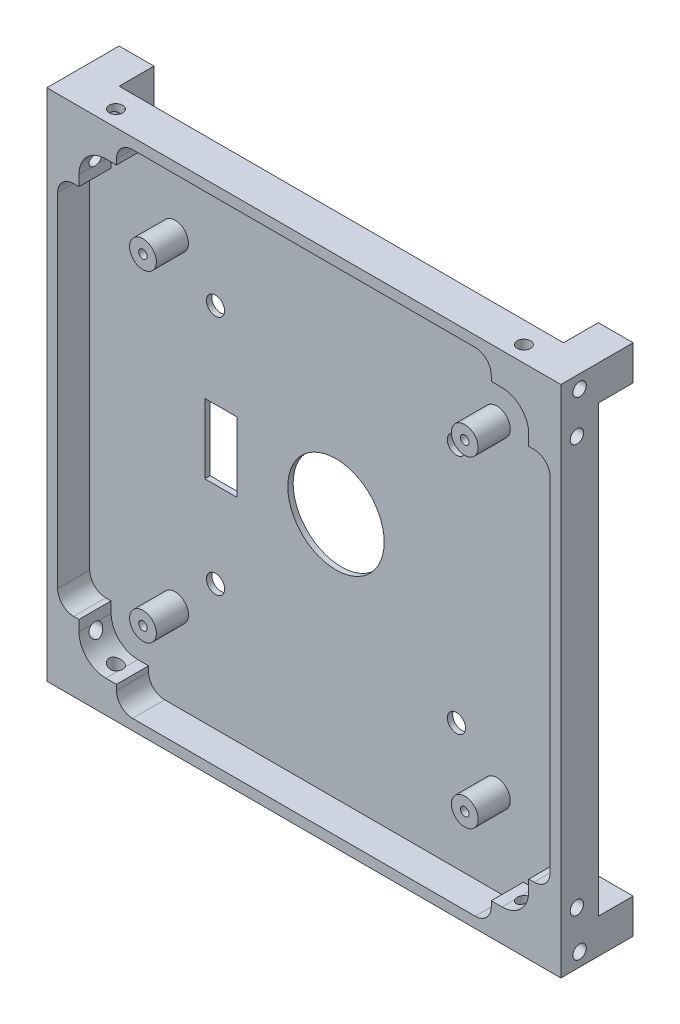
SolidWorks part; units mm, degrees
material "7075-T6 (SN)"
ref_plane "Front Plane" through (0, 0, 0) normal (0, 0, 1) x (1, 0, 0)
ref_plane "Top Plane" through (0, 0, 0) normal (0, 1, 0) x (1, 0, 0)
ref_plane "Right Plane" through (0, 0, 0) normal (1, 0, 0) x (0, 0, -1)
sketch "Sketch1" plane through (0, 0, 0) normal (0, 0, 1) x (1, 0, 0)
  line L1 (48, -48) -> (-48, -48)
  line L2 (48, -48) -> (48, 48)
  line L3 (48, 48) -> (-48, 48)
  line L4 (-48, -48) -> (-48, 48)
  line L5 (48, -48) -> (-48, 48) construction
  line L6 (48, 48) -> (-48, -48) construction
  point P0 (0, 0)
  dimension "D1" = 96
  dimension "D2" = 96
extrude "Boss-Extrude1" add sketch "Sketch1" along normal blind 2
sketch "Sketch2" plane through (0, 0, 2) normal (0, 0, 1) x (1, 0, 0)
  line L0 (48, 48) -> (-48, 48) construction
  line L1 (37, -42) -> (-37, -42)
  line L2 (42, -37) -> (42, 37)
  line L3 (37, 42) -> (-37, 42)
  line L4 (-42, -37) -> (-42, 37)
  line L5 (42, -42) -> (-42, 42) construction
  line L6 (42, 42) -> (-42, -42) construction
  line L7 (48, -48) -> (48, 48) construction
  line L12 (-48, 48) -> (-48, -48)
  line L13 (-48, -48) -> (48, -48)
  line L14 (48, -48) -> (48, 48)
  line L15 (48, 48) -> (-48, 48)
  line L16 (-48, 48) -> (-48, -48)
  line L17 (-48, -48) -> (48, -48)
  line L18 (48, -48) -> (48, 48)
  line L19 (48, 48) -> (-48, 48)
  arc A0 (-37, -42) -> (-42, -37) centre (-37, -37) cw
  arc A1 (37, -42) -> (42, -37) centre (37, -37) ccw
  arc A2 (42, 37) -> (37, 42) centre (37, 37) ccw
  arc A3 (-37, 42) -> (-42, 37) centre (-37, 37) ccw
  point P0 (0, 0)
  dimension "D4" = 5
  dimension "D1" = 6
  dimension "D2" = 6
extrude "Boss-Extrude2" add sketch "Sketch2" along normal blind 5
sketch "Sketch4" plane through (0, 0, 7) normal (0, 0, 1) x (1, 0, 0)
  line L0 (-41.5, 41.5) -> (41.5, -41.5) construction
  line L1 (-41.5, 41.5) -> (41.5, 41.5)
  line L2 (-41.5, 41.5) -> (-41.5, -41.5)
  line L3 (-41.5, -41.5) -> (41.5, -41.5)
  line L4 (41.5, 41.5) -> (41.5, -41.5)
  point P4 (0, 0)
  dimension "D1" = 83
  dimension "D2" = 83
sketch "Sketch3" plane through (0, 0, 0) normal (0, 0, -1) x (-1, 0, 0)
  line L1 (-48, 48) -> (-41.5, 48)
  line L2 (-48, 48) -> (-48, 41.5)
  line L3 (-48, 41.5) -> (-41.5, 41.5)
  line L4 (-41.5, 48) -> (-41.5, 41.5)
  line L5 (48, 48) -> (41.5, 48)
  line L6 (48, 48) -> (48, 41.5)
  line L7 (48, 41.5) -> (41.5, 41.5)
  line L8 (41.5, 48) -> (41.5, 41.5)
  line L9 (-48, -48) -> (-41.5, -48)
  line L10 (-48, -48) -> (-48, -41.5)
  line L11 (-48, -41.5) -> (-41.5, -41.5)
  line L12 (-41.5, -48) -> (-41.5, -41.5)
  line L13 (48, -48) -> (41.5, -48)
  line L14 (48, -48) -> (48, -41.5)
  line L15 (48, -41.5) -> (41.5, -41.5)
  line L16 (41.5, -48) -> (41.5, -41.5)
  dimension "D1" = 6.5
  dimension "D2" = 6.5
  dimension "D3" = 6.5
  dimension "D4" = 6.5
extrude "Boss-Extrude3" add sketch "Sketch3" along normal blind 6.5
sketch "Sketch5" plane through (0, 0, 0) normal (0, 0, -1) x (-1, 0, 0)
  circle A0 centre (0, 0) radius 9
  dimension "D1" = 18
extrude "Cut-Extrude1" cut sketch "Sketch5" against normal blind 10
sketch "Sketch6" plane through (-48, 0, 0) normal (-1, 0, 0) x (0, 0, 1)
  line L0 (-6.5, -45.5) -> (7, -45.5) construction
  line L2 (7, 48) -> (7, -48) construction
  line L3 (-6.5, 45.5) -> (7, 45.5) construction
  line L5 (7, 48) -> (-6.5, 48) construction
  line L6 (7, -48) -> (-6.5, -48) construction
  point P6 (3.5, -45.5)
  point P11 (3.5, 45.5)
  dimension "D1" = 3.5
  dimension "D2" = 3.5
  dimension "D3" = 2.5
  dimension "D4" = 2.5
hole_wizard "M3 Tapped Hole1" positions "3DSketch1" profile "Sketch7" tap size "M3" standard "ISO"
sketch3d "3DSketch1"
  point P0 (-48, 45.5, 3.5)
  point P3 (-48, -45.5, 3.5)
sketch "Sketch7" plane through (-48, 45.5, 3.5) normal (0, 1, 0) x (0, 0, 1)
  line L0 (0, 0) -> (0, 10.2511)
  line L1 (0, 10.2511) -> (1.25, 9.5)
  line L2 (1.25, 9.5) -> (1.25, 0)
  line L5 (1.25, 0) -> (0, 0)
  line L10 (0, 10.2511) -> (-1.25, 9.5) construction
  line L11 (0, -6.35) -> (0, 107.95) construction
  dimension "Tap Drill Dia." = 2.5
  dimension "Tap Drill Depth" = 9.5
  dimension "Drill Angle" = 118
cosmetic thread "Hole Thread1" parameters "D1"=8, "D2"=3
cosmetic thread "Hole Thread2" parameters "D1"=8, "D2"=3
mirror "Mirror1" about plane through (0, 0, 0) normal (1, 0, 0) of "M3 Tapped Hole1"
sketch "Sketch8" plane through (48, 0, 0) normal (1, 0, 0) x (0, 0, -1)
  point P0 (-4, -38.0996)
  point P1 (-4, 38.1004)
hole_wizard "M3 Tapped Hole2" positions "3DSketch2" profile "Sketch10" tap size "M3" standard "ISO"
sketch3d "3DSketch2"
  point P0 (48, 38.1004, 4)
  point P3 (48, -38.0996, 4)
sketch "Sketch10" plane through (48, 38.1004, 4) normal (0, 1, 0) x (0, 0, -1)
  line L0 (0, 0) -> (0, 9.2511)
  line L1 (0, 9.2511) -> (1.25, 8.5)
  line L2 (1.25, 8.5) -> (1.25, 0)
  line L5 (1.25, 0) -> (0, 0)
  line L10 (0, 9.2511) -> (-1.25, 8.5) construction
  line L11 (0, -6.35) -> (0, 107.95) construction
  dimension "Tap Drill Dia." = 2.5
  dimension "Tap Drill Depth" = 8.5
  dimension "Drill Angle" = 118
cosmetic thread "Hole Thread3" parameters "D1"=6, "D2"=3
cosmetic thread "Hole Thread4" parameters "D1"=6, "D2"=3
ref_axis "Axis1" through (0, 0, 2) along (0, 0, -1)
pattern_circular "CirPattern1" count 4 every 90 about axis through (0, 0, 2) along (0, 0, -1) of "M3 Tapped Hole2"
sketch "Sketch11" plane through (0, 0, 7) normal (0, 0, 1) x (1, 0, 0)
  line L0 (-37, -42) -> (37, -42) construction
  line L1 (32, -46) -> (-32, -46)
  line L2 (35, -43) -> (35, -42)
  line L3 (35, -42) -> (-35, -42)
  line L4 (-35, -43) -> (-35, -42)
  line L5 (-48, -48) -> (48, -48) construction
  line L6 (48, -48) -> (48, 48) construction
  line L7 (-48, 48) -> (-48, -48) construction
  line L8 (48, 48) -> (-48, 48) construction
  line L9 (-42, -35) -> (-43, -35)
  line L10 (-42, -35) -> (-42, 35)
  line L11 (-42, 35) -> (-43, 35)
  line L12 (-37, -42) -> (37, -42)
  line L13 (42, -37) -> (42, 37)
  line L14 (37, 42) -> (-37, 42)
  line L15 (-42, 37) -> (-42, -37)
  line L16 (-37, -42) -> (37, -42)
  line L17 (42, -37) -> (42, 37)
  line L18 (37, 42) -> (-37, 42)
  line L19 (-42, 37) -> (-42, -37)
  line L20 (-46, -32) -> (-46, 32)
  arc A0 (-43, 35) -> (-46, 32) centre (-43, 32) ccw
  arc A1 (-43, -35) -> (-46, -32) centre (-43, -32) cw
  arc A2 (-32, -46) -> (-35, -43) centre (-32, -43) cw
  arc A3 (32, -46) -> (35, -43) centre (32, -43) ccw
  arc A4 (-42, -37) -> (-37, -42) centre (-37, -37) ccw
  arc A5 (37, -42) -> (42, -37) centre (37, -37) ccw
  arc A6 (42, 37) -> (37, 42) centre (37, 37) ccw
  arc A7 (-37, 42) -> (-42, 37) centre (-37, 37) ccw
  arc A8 (-42, -37) -> (-37, -42) centre (-37, -37) ccw
  arc A9 (37, -42) -> (42, -37) centre (37, -37) ccw
  arc A10 (42, 37) -> (37, 42) centre (37, 37) ccw
  arc A11 (-37, 42) -> (-42, 37) centre (-37, 37) ccw
  point P10 (-35, -42.5)
  line M21 (37, -42) -> (-37, -42)
  line M23 (-42, -37) -> (-42, 37)
  dimension "D1" = 2
  dimension "D8" = 3
  dimension "D2" = 13
  dimension "D3" = 13
  dimension "D5" = 13
  dimension "D6" = 13
  dimension "D7" = 2
extrude "Cut-Extrude2" cut sketch "Sketch11" against normal up to surface (5 mm away) contours A1 L9 L11 A0 L20 M23 | L1 A3 L2 L4 A2 M21 region at (0, -43.9814, 7) region at (-43.9814, 0, 7) up to face at (9, 0, 2)
pattern_circular "CirPattern2" count 2 every 180 about axis through (0, 0, 2) along (0, 0, -1) of "Cut-Extrude2"
sketch "Sketch12" plane through (0, 0, 2) normal (0, 0, 1) x (1, 0, 0)
  line L20 (-37, -42) -> (-35, -42)
  line L21 (-35, -42) -> (-35, -43)
  line L22 (-32, -46) -> (32, -46)
  line L23 (35, -43) -> (35, -42)
  line L24 (35, -42) -> (37, -42)
  line L25 (42, -37) -> (42, -35)
  line L26 (42, -35) -> (43, -35)
  line L27 (46, -32) -> (46, 32)
  line L28 (43, 35) -> (42, 35)
  line L29 (42, 35) -> (42, 37)
  line L30 (37, 42) -> (35, 42)
  line L31 (35, 42) -> (35, 43)
  line L32 (32, 46) -> (-32, 46)
  line L33 (-35, 43) -> (-35, 42)
  line L34 (-35, 42) -> (-37, 42)
  line L35 (-42, 37) -> (-42, 35)
  line L36 (-42, 35) -> (-43, 35)
  line L37 (-46, 32) -> (-46, -32)
  line L38 (-43, -35) -> (-42, -35)
  line L39 (-42, -35) -> (-42, -37)
  line L40 (-37, -42) -> (-35, -42)
  line L41 (-35, -42) -> (-35, -43)
  line L42 (-32, -46) -> (32, -46)
  line L43 (35, -43) -> (35, -42)
  line L44 (35, -42) -> (37, -42)
  line L45 (42, -37) -> (42, -35)
  line L46 (42, -35) -> (43, -35)
  line L47 (46, -32) -> (46, 32)
  line L48 (43, 35) -> (42, 35)
  line L49 (42, 35) -> (42, 37)
  line L50 (37, 42) -> (35, 42)
  line L51 (35, 42) -> (35, 43)
  line L52 (32, 46) -> (-32, 46)
  line L53 (-35, 43) -> (-35, 42)
  line L54 (-35, 42) -> (-37, 42)
  line L55 (-42, 37) -> (-42, 35)
  line L56 (-42, 35) -> (-43, 35)
  line L57 (-46, 32) -> (-46, -32)
  line L58 (-43, -35) -> (-42, -35)
  line L59 (-42, -35) -> (-42, -37)
  arc A12 (-42, -37) -> (-37, -42) centre (-37, -37) ccw
  arc A13 (-35, -43) -> (-32, -46) centre (-32, -43) ccw
  arc A14 (32, -46) -> (35, -43) centre (32, -43) ccw
  arc A15 (37, -42) -> (42, -37) centre (37, -37) ccw
  arc A16 (43, -35) -> (46, -32) centre (43, -32) ccw
  arc A17 (46, 32) -> (43, 35) centre (43, 32) ccw
  arc A18 (42, 37) -> (37, 42) centre (37, 37) ccw
  arc A19 (35, 43) -> (32, 46) centre (32, 43) ccw
  arc A20 (-32, 46) -> (-35, 43) centre (-32, 43) ccw
  arc A21 (-37, 42) -> (-42, 37) centre (-37, 37) ccw
  arc A22 (-43, 35) -> (-46, 32) centre (-43, 32) ccw
  arc A23 (-46, -32) -> (-43, -35) centre (-43, -32) ccw
  arc A24 (-42, -37) -> (-37, -42) centre (-37, -37) ccw
  arc A25 (-35, -43) -> (-32, -46) centre (-32, -43) ccw
  arc A26 (32, -46) -> (35, -43) centre (32, -43) ccw
  arc A27 (37, -42) -> (42, -37) centre (37, -37) ccw
  arc A28 (43, -35) -> (46, -32) centre (43, -32) ccw
  arc A29 (46, 32) -> (43, 35) centre (43, 32) ccw
  arc A30 (42, 37) -> (37, 42) centre (37, 37) ccw
  arc A31 (35, 43) -> (32, 46) centre (32, 43) ccw
  arc A32 (-32, 46) -> (-35, 43) centre (-32, 43) ccw
  arc A33 (-37, 42) -> (-42, 37) centre (-37, 37) ccw
  arc A34 (-43, 35) -> (-46, 32) centre (-43, 32) ccw
  arc A35 (-46, -32) -> (-43, -35) centre (-43, -32) ccw
  dimension "D1" = 0
extrude "Cut-Extrude3" cut sketch "Sketch12" against normal blind 1
sketch "Sketch13" plane through (0, 0, 7) normal (0, 0, 1) x (1, 0, 0)
  line L4 (48, 48) -> (-48, 48)
  line L5 (-48, 48) -> (-48, -48)
  line L6 (-48, -48) -> (48, -48)
  line L7 (48, -48) -> (48, 48)
  line L8 (48, 48) -> (-48, 48)
  line L9 (-48, 48) -> (-48, -48)
  line L10 (-48, -48) -> (48, -48)
  line L11 (48, -48) -> (48, 48)
  dimension "D1" = 0
extrude "Cut-Extrude4" [suppressed] cut sketch "Sketch13" against normal blind 1
sketch "Sketch14" plane through (0, 0, 0) normal (0, 0, -1) x (-1, 0, 0)
  circle A0 centre (0, 0) radius 20
  text T0 "MSSG       -      EYE-SAT" font "Impact" height 4
  dimension "D1" = 40
sketch "Sketch15" plane through (0, 0, 1) normal (0, 0, 1) x (1, 0, 0)
  line L0 (0, 0) -> (-35.5279, 35.5279) construction
  line L1 (0, 0) -> (-32.9127, -32.9127) construction
  circle A0 centre (0, 0) radius 42.5 construction
  circle A1 centre (-30.052, 30.052) radius 2.5
  point P2 (30.052, 30.052)
  point P6 (30.052, -30.052)
  point P9 (-30.052, -30.052)
  point P10 (-30.052, 30.052)
extrude "Boss-Extrude4" add sketch "Sketch15" along normal blind 6
pattern_circular "CirPattern3" count 4 over 360 about axis through (0, 0, 2) along (0, 0, -1) of "Boss-Extrude4" reverse direction yes
hole_wizard "Tap Drill for M2x0.4 Tap1" positions "3DSketch3" profile "Sketch16" hole size "M2x0.4" standard "ANSI Metric"
sketch3d "3DSketch3"
  line L3 (-30.052, 30.052, 7) -> (-30.052, 30.052, 1) construction
  point P0 (-30.052, 30.052, 7)
  point P17 (-30.052, 30.052, 7)
sketch "Sketch16" plane through (-30.052, 30.052, 7) normal (1, 0, 0) x (0, -1, 0)
  line L0 (0, 0) -> (0, 6.4797)
  line L1 (0, 6.4797) -> (0.8, 5.999)
  line L2 (0.8, 5.999) -> (0.8, 0)
  line L5 (0.8, 0) -> (0, 0)
  line L10 (0, 6.4797) -> (-0.8, 5.999) construction
  line L11 (0, -6.35) -> (0, 107.95) construction
  dimension "Hole Dia." = 1.6
  dimension "Hole Depth" = 5.999
  dimension "Drill Angle" = 118
pattern_circular "CirPattern4" count 4 over 360 about axis through (0, 0, 2) along (0, 0, -1) of "Tap Drill for M2x0.4 Tap1"
sketch "Sketch17" plane through (0, 0, 1) normal (0, 0, 1) x (1, 0, 0)
  line L1 (-18.5, -6.5) -> (-24.5, -6.5)
  line L2 (-18.5, -6.5) -> (-18.5, 6.5)
  line L3 (-18.5, 6.5) -> (-24.5, 6.5)
  line L4 (-24.5, -6.5) -> (-24.5, 6.5)
  line L5 (-18.5, -6.5) -> (-24.5, 6.5) construction
  line L6 (-18.5, 6.5) -> (-24.5, -6.5) construction
  point P0 (-21.5, 0)
  point P5 (-24.3471, 0)
  point P6 (-23.3558, 0)
  dimension "D1" = 13
  dimension "D2" = 6
  dimension "D3" = 21.5
extrude "Cut-Extrude5" cut sketch "Sketch17" against normal blind 10
hole_wizard "M3 Clearance Hole1" positions "3DSketch4" profile "Sketch18" hole size "M3" standard "ANSI Metric" end condition through all
sketch3d "3DSketch4"
  point P0 (-22.5, -22.5, 1)
  point P3 (0, 0, 0)
sketch "Sketch18" plane through (-22.5, -22.5, 1) normal (1, 0, 0) x (0, -1, 0)
  line L0 (0, 0) -> (0, 7.5)
  line L1 (0, 7.5) -> (1.7, 7.5)
  line L2 (1.7, 7.5) -> (1.7, 0)
  line L5 (1.7, 0) -> (0, 0)
  line L11 (0, -6.35) -> (0, 107.95) construction
  dimension "Thru Hole Dia." = 3.4
  dimension "Thru Hole Depth" = 7.5
pattern_circular "CirPattern5" count 4 over 360 about axis through (0, 0, 2) along (0, 0, -1) of "M3 Clearance Hole1"
equation "\"D2@Sketch1\"=\"D1@Sketch1\""
equation "\"thickness\" = 2"
equation "\"D1@Boss-Extrude1\"=\"thickness\""
equation "\"D2@Sketch2\"=\"D1@Sketch2\""
equation "\"D2@Sketch3\"=\"D1@Sketch3\""
equation "\"D3@Sketch3\"=\"D1@Sketch3\""
equation "\"D4@Sketch3\"=\"D1@Sketch3\""
equation "\"D2@Sketch4\"=\"D1@Sketch4\""
equation "\"D2@Sketch6\"=\"D1@Sketch6\""
equation "\"D4@Sketch6\"=\"D3@Sketch6\""
equation "\"D3@Sketch11\"=\"D2@Sketch11\""
equation "\"D5@Sketch11\"=\"D2@Sketch11\""
equation "\"D6@Sketch11\"=\"D2@Sketch11\""
equation "\"D7@Sketch11\"=\"D1@Sketch11\""
